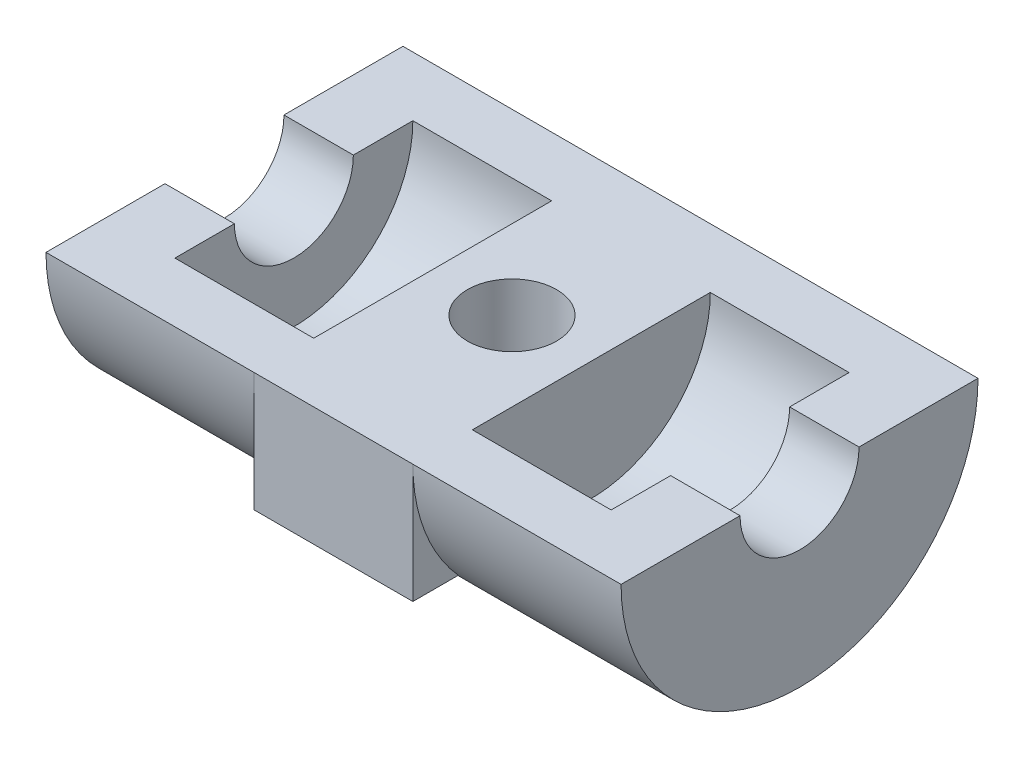
SolidWorks part; units mm, degrees
ref_plane "Front Plane" through (0, 0, 0) normal (0, 0, 1) x (1, 0, 0)
ref_plane "Top Plane" through (0, 0, 0) normal (0, 1, 0) x (1, 0, 0)
ref_plane "Right Plane" through (0, 0, 0) normal (1, 0, 0) x (0, 0, -1)
sketch "Sketch1" plane through (0, 0, 0) normal (0, 0, 1) x (1, 0, 0)
  line L0 (-39.0878, 0) -> (44.4257, 0) construction
  line L1 (-14.5, 9) -> (14.5, 9)
  line L2 (-14.5, 9) -> (-14.5, 3)
  line L3 (-14.5, 3) -> (-11, 3)
  line L4 (-11, 3) -> (-11, 6)
  line L5 (-11, 6) -> (11, 6)
  line L7 (0, -55) -> (0, 55) construction
  line L8 (11, 3) -> (11, 6)
  line L9 (14.5, 3) -> (11, 3)
  line L10 (14.5, 9) -> (14.5, 3)
  point P6 (0, 7.5)
  dimension "D1" = 3
  dimension "D2" = 9
  dimension "D3" = 3.5
  dimension "D4" = 11
  dimension "D5" = 3
revolve "Revolve1" add sketch "Sketch1" angle 360 about L0
sketch "Sketch4" plane through (0, 0, 0) normal (0, 1, 0) x (1, 0, 0)
  line L0 (-14.5, -9) -> (14.5, -9) construction
  line L1 (-4, 9) -> (4, 9)
  line L2 (-4, 9) -> (-4, -9)
  line L3 (-4, -9) -> (4, -9)
  line L4 (4, 9) -> (4, -9)
  line L5 (-4, 9) -> (4, -9) construction
  line L6 (-4, -9) -> (4, 9) construction
  circle A0 centre (0, 0) radius 2.25
  dimension "D1" = 4.5
  dimension "D2" = 8
extrude "Cut-Extrude1" cut sketch "Sketch4" against normal blind 10 and the other way blind 10 contours A0 | A0 region at (0, 0, 0)
extrude "Boss-Extrude1" add sketch "Sketch4<3>" along normal mid plane 12 contours A0 | L4 L3 L2 L1 region at (0, 0, 0)
sketch "Sketch4<3>" plane through (0, 0, 0) normal (0, 1, 0) x (1, 0, 0) same geometry as "Sketch4"
sketch "Sketch5" plane through (-14.5, 0, 0) normal (-1, 0, 0) x (0, 0, 1)
  line L0 (-9.2845, 0) -> (10.3609, 0)
extrude "Cut-Extrude2" cut sketch "Sketch5" against normal through all and the other way through all
